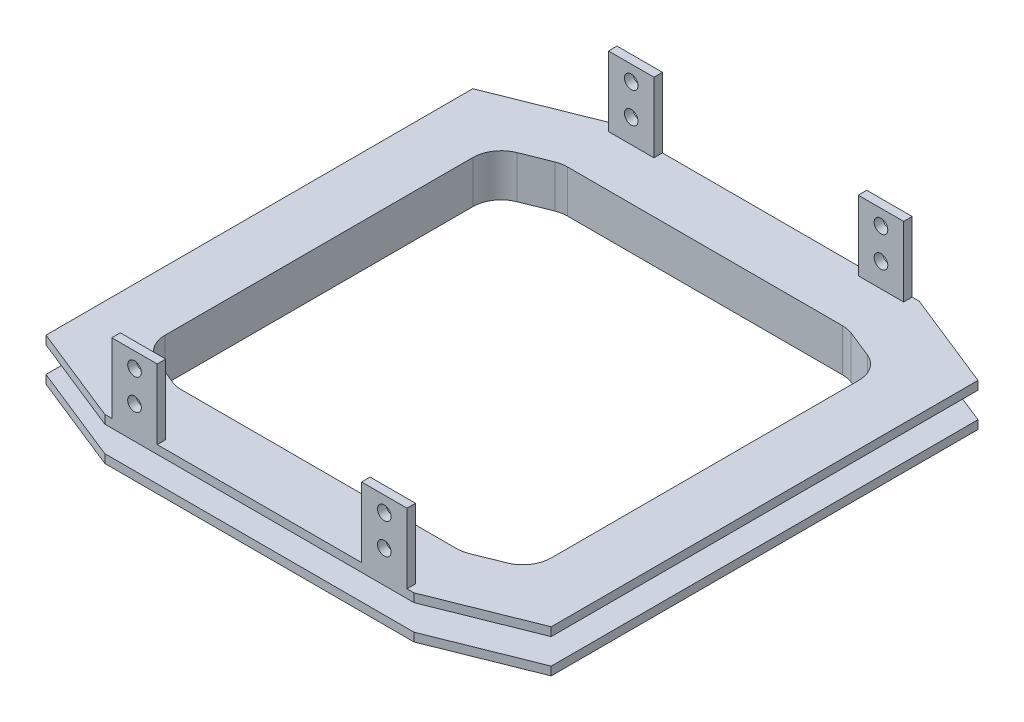
SolidWorks part; units mm, degrees
ref_plane "Front Plane" through (0, 0, 0) normal (0, 0, 1) x (1, 0, 0)
ref_plane "Top Plane" through (0, 0, 0) normal (0, 1, 0) x (1, 0, 0)
ref_plane "Right Plane" through (0, 0, 0) normal (1, 0, 0) x (0, 0, -1)
sketch "Sketch1" plane through (0, 0, 0) normal (0, 1, 0) x (1, 0, 0)
  line L5 (-35.5, 0) -> (0, 0) construction
  line L6 (-25.5, -35.5) -> (25.5, -35.5)
  line L10 (-35.5, -31.5) -> (-35.5, 31.5)
  line L11 (-25.5, 35.5) -> (25.5, 35.5)
  line L12 (35.5, -31.5) -> (35.5, 31.5)
  line L13 (0, 0) -> (0, 35.5) construction
  line L14 (25.5, -35.5) -> (35.5, -31.5)
  line L15 (25.5, 35.5) -> (35.5, 31.5)
  line L16 (-25.5, -35.5) -> (-35.5, -31.5)
  line L17 (-25.5, 35.5) -> (-35.5, 31.5)
  point P0 (0, 0)
  point P4 (35.5, -35.5)
  dimension "D3" = 4
  dimension "D2" = 10
  dimension "D4" = 71
extrude "Boss-Extrude1" add sketch "Sketch1" along normal mid plane 4.5
sketch "Sketch2" plane through (0, 2.25, 0) normal (0, 1, 0) x (1, 0, 0)
  line L16 (27.2332, -44.5) -> (44.5, -37.5933)
  line L17 (44.5, -37.5933) -> (44.5, 37.5933)
  line L18 (44.5, 37.5933) -> (27.2332, 44.5)
  line L19 (27.2332, 44.5) -> (-27.2332, 44.5)
  line L20 (-27.2332, 44.5) -> (-44.5, 37.5933)
  line L21 (-44.5, 37.5933) -> (-44.5, -37.5933)
  line L22 (-44.5, -37.5933) -> (-27.2332, -44.5)
  line L23 (-27.2332, -44.5) -> (27.2332, -44.5)
  line L24 (27.2332, -44.5) -> (44.5, -37.5933)
  line L25 (44.5, -37.5933) -> (44.5, 37.5933)
  line L26 (44.5, 37.5933) -> (27.2332, 44.5)
  line L27 (27.2332, 44.5) -> (-27.2332, 44.5)
  line L28 (-27.2332, 44.5) -> (-44.5, 37.5933)
  line L29 (-44.5, 37.5933) -> (-44.5, -37.5933)
  line L30 (-44.5, -37.5933) -> (-27.2332, -44.5)
  line L31 (-27.2332, -44.5) -> (27.2332, -44.5)
  dimension "D1" = 9
extrude "Boss-Extrude2" add sketch "Sketch2" along normal blind 1.5
mirror "Mirror1" about plane through (0, 0, 0) normal (0, 1, 0) of "Boss-Extrude2"
sketch "Sketch3" plane through (0, 0, 0) normal (0, 1, 0) x (1, 0, 0)
  line L16 (-25.2111, -34) -> (25.2111, -34)
  line L17 (25.2111, -34) -> (34, -30.4845)
  line L18 (34, -30.4845) -> (34, 30.4845)
  line L19 (34, 30.4845) -> (25.2111, 34)
  line L20 (25.2111, 34) -> (-25.2111, 34)
  line L21 (-25.2111, 34) -> (-34, 30.4845)
  line L22 (-34, 30.4845) -> (-34, -30.4845)
  line L23 (-34, -30.4845) -> (-25.2111, -34)
  line L24 (-25.2111, -34) -> (25.2111, -34)
  line L25 (25.2111, -34) -> (34, -30.4845)
  line L26 (34, -30.4845) -> (34, 30.4845)
  line L27 (34, 30.4845) -> (25.2111, 34)
  line L28 (25.2111, 34) -> (-25.2111, 34)
  line L29 (-25.2111, 34) -> (-34, 30.4845)
  line L30 (-34, 30.4845) -> (-34, -30.4845)
  line L31 (-34, -30.4845) -> (-25.2111, -34)
  dimension "D1" = 10.5
extrude "Cut-Extrude1" cut sketch "Sketch3" against normal through all both and the other way through all
sketch "Sketch5" plane through (0, 0, 0) normal (0, 0, 1) x (1, 0, 0)
  line L0 (0, 0) -> (0, 28.4264) construction
  line L1 (-27.2332, 3.75) -> (27.2332, 3.75) construction
  line L2 (-26, 3.75) -> (-18, 3.75)
  line L3 (-26, 3.75) -> (-26, 16.05)
  line L4 (-26, 16.05) -> (-18, 16.05)
  line L5 (-18, 3.75) -> (-18, 16.05)
  line L6 (-22, 16.05) -> (-22, 9.7096) construction
  line L7 (18, 3.75) -> (18, 16.05)
  line L8 (26, 16.05) -> (18, 16.05)
  line L9 (26, 3.75) -> (26, 16.05)
  line L10 (26, 3.75) -> (18, 3.75)
  dimension "D1" = 22
  dimension "D3" = 12.3
  dimension "D2" = 8
extrude "Boss-Extrude3" add sketch "Sketch5" against normal blind 1.5 from surface starting at face at (0, 3, 44.5)
extrude "Boss-Extrude4" add sketch "Sketch5<2>" along normal blind 1.5 from surface starting at face at (0, 3, -44.5)
sketch "Sketch5<2>" plane through (0, 0, 0) normal (0, 0, 1) x (1, 0, 0) same geometry as "Sketch5"
sketch "Sketch6" plane through (0, 0, 0) normal (0, 0, 1) x (1, 0, 0)
  line L0 (-22, 16.05) -> (-22, 13.35) construction
  line L1 (-18, 16.05) -> (-26, 16.05) construction
  line L2 (0, 0) -> (0, 25.5714) construction
  line L3 (-22, 13.35) -> (-22, 7.95) construction
  circle A0 centre (-22, 13.35) radius 1.2
  circle A1 centre (22, 13.35) radius 1.2
  circle A2 centre (-22, 7.95) radius 1.2
  circle A3 centre (22, 7.95) radius 1.2
  dimension "D1" = 2.4
  dimension "D2" = 2.7
  dimension "D3" = 5.4
extrude "Cut-Extrude3" cut sketch "Sketch6" against normal through all both and the other way through all
fillet "Fillet1" radius 1 24 edges at (35.5, 0, 31.5) (25.5, 0, 35.5) (0, 2.25, -35.5) (0, -2.25, -35.5) (35.5, 2.25, 0) (35.5, -2.25, 0) (-35.5, 2.25, 0) (-35.5, -2.25, 0) (0, 2.25, 35.5) (0, -2.25, 35.5) (-25.5, 0, -35.5) (-30.5, 2.25, -33.5) (-35.5, 0, -31.5) (-30.5, -2.25, -33.5) (35.5, 0, -31.5) (30.5, 2.25, -33.5) (25.5, 0, -35.5) (30.5, -2.25, -33.5) (30.5, 2.25, 33.5) (30.5, -2.25, 33.5) (-35.5, 0, 31.5) (-30.5, 2.25, 33.5) (-25.5, 0, 35.5) (-30.5, -2.25, 33.5)
fillet "Fillet2" radius 5 8 edges at (-25.2111, 0, -34) (-34, 0, -30.4845) (25.2111, 0, -34) (34, 0, -30.4845) (25.2111, 0, 34) (34, 0, 30.4845) (-25.2111, 0, 34) (-34, 0, 30.4845)
